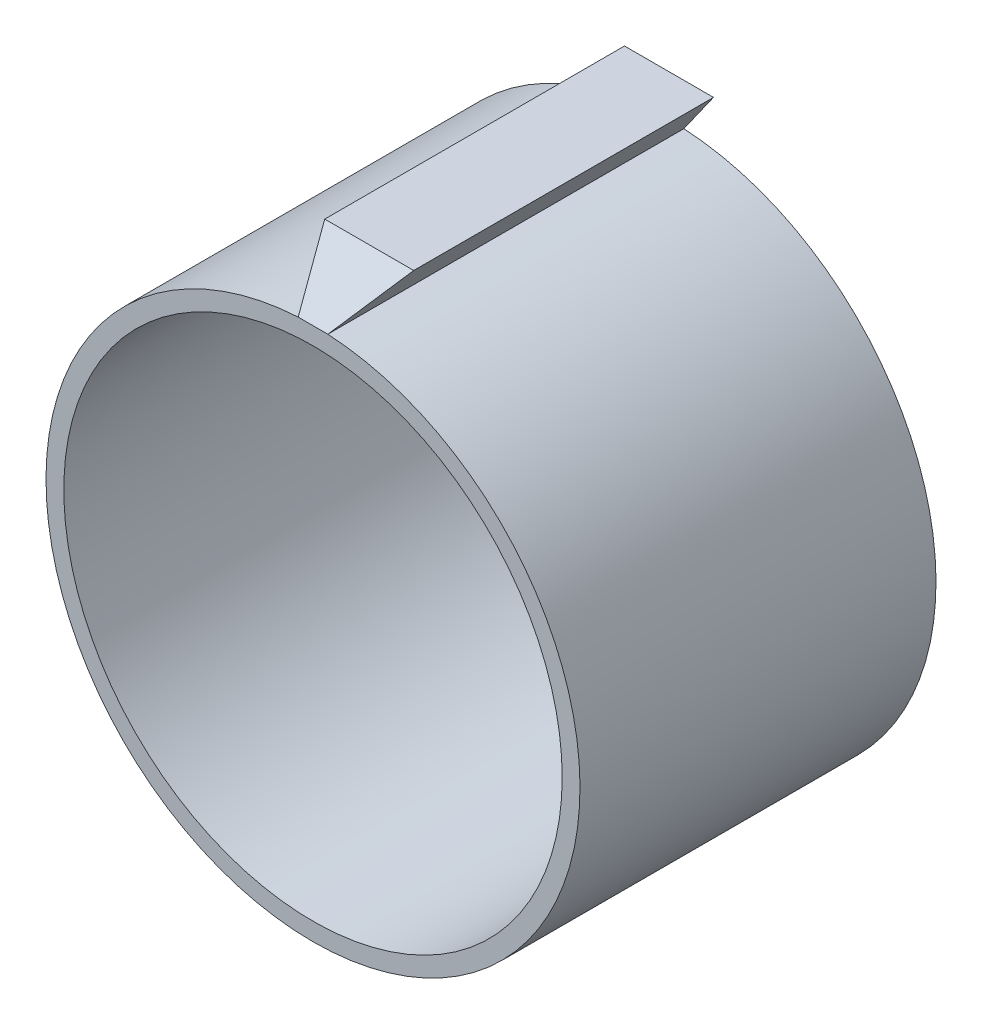
SolidWorks part; units mm, degrees
ref_plane "Front Plane" through (0, 0, 0) normal (0, 0, 1) x (1, 0, 0)
ref_plane "Top Plane" through (0, 0, 0) normal (0, 1, 0) x (1, 0, 0)
ref_plane "Right Plane" through (0, 0, 0) normal (1, 0, 0) x (0, 0, -1)
sketch "Sketch1" plane through (0, 0, 0) normal (0, 0, 1) x (1, 0, 0)
  line L0 (0, 42) -> (0, 52) construction
  line L3 (-7.5, 52) -> (7.5, 52)
  line L4 (-7.5, 52) -> (-2.5, 44.9305)
  line L5 (7.5, 52) -> (2.5, 44.9305)
  circle A0 centre (0, 0) radius 42
  arc A1 (-25, 33.7491) -> (25, 33.7491) centre (0, 0) cw
  arc A2 (26.7857, 36.1597) -> (-2.5, 44.9305) centre (0, 0) cw
  arc A3 (2.5, 44.9305) -> (26.7857, 36.1597) centre (0, 0) cw
  arc A4 (-26.7857, 36.1597) -> (26.7857, 36.1597) centre (0, 0) cw construction
  point P3 (-25, 33.7491)
  point P4 (25, 33.7491)
  point P16 (0, 52)
  point P18 (0, 47)
  dimension "D1" = 84
  dimension "D2" = 50
  dimension "D3" = 10
  dimension "D5" = 15
  dimension "D6" = 2.5
  dimension "D4" = 3
extrude "Boss-Extrude1" add sketch "Sketch1" along normal blind 60 contours A3 L5 L3 L4 A2 A0 region at (0, 50.6768, 0)
sketch "Sketch2" plane through (0, 0, 0) normal (1, 0, 0) x (0, 0, -1)
  line L0 (-60, 44.9305) -> (-50.5251, 52)
  line L1 (-60, 52) -> (0, 52) construction
  line L2 (-50.5251, 52) -> (-60, 52)
  line L3 (-60, 52) -> (-60, 44.9305)
extrude "Cut-Extrude1" cut sketch "Sketch2" along normal up to surface and the other way up to surface up to face at (5, 48.4653, 30) other way up to face at (-5, 48.4653, 30)
